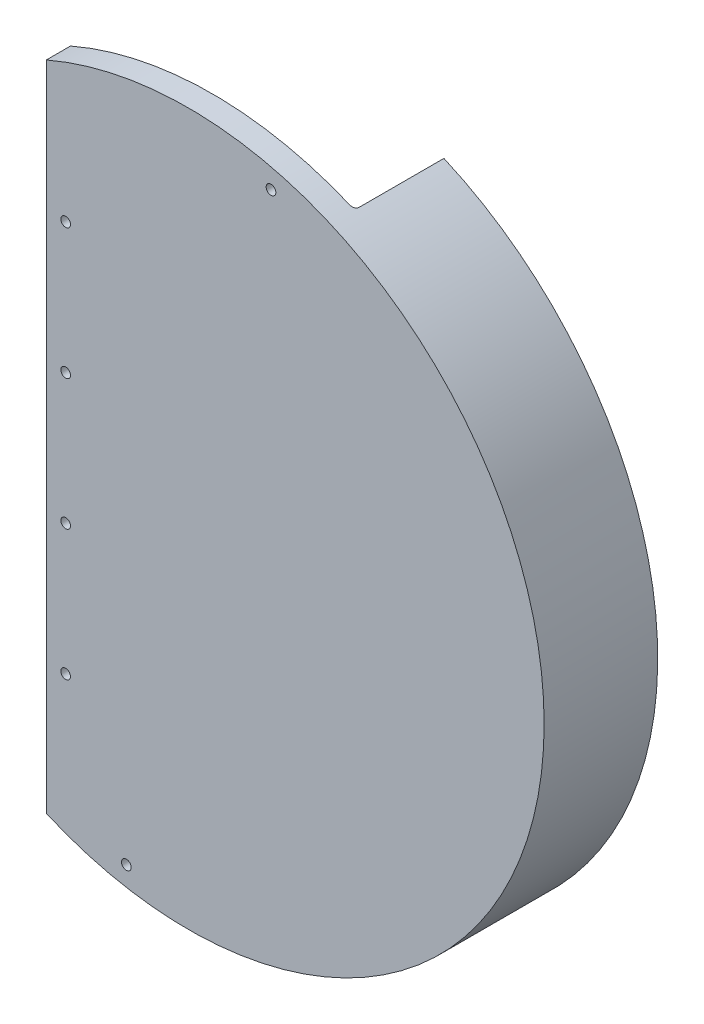
SolidWorks part; units mm, degrees
ref_plane "Front Plane" through (0, 0, 0) normal (0, 0, 1) x (1, 0, 0)
ref_plane "Top Plane" through (0, 0, 0) normal (0, 1, 0) x (1, 0, 0)
ref_plane "Right Plane" through (0, 0, 0) normal (1, 0, 0) x (0, 0, -1)
sketch "Sketch1" plane through (0, 0, 0) normal (0, 0, 1) x (1, 0, 0)
  line L0 (0, -67.5) -> (0, 67.5)
  line L1 (8, -62.0361) -> (8, 62.0361) construction
  line L2 (29.3823, 0) -> (0, -67.5) construction
  line L3 (29.3823, 0) -> (24.8583, -73.4786) construction
  line L4 (20, 73.0174) -> (20, 64.9435) construction
  line L5 (35, 73.4031) -> (35, 65.3768) construction
  line L6 (58.7646, 67.5) -> (55.5716, 60.1648) construction
  line L7 (0, 0) -> (8, 0) construction
  line L8 (4, 69.1036) -> (4, -69.1036) construction
  line L9 (0, 67.5) -> (-23.4948, 67.5) construction
  line L10 (-23.4948, 67.5) -> (-23.4948, 40.5) construction
  line L11 (-23.4948, 40.5) -> (-23.4948, 13.5) construction
  line L12 (-23.4948, 13.5) -> (-23.4948, 40.5) construction
  line L13 (-23.4948, 13.5) -> (-23.4948, -13.5) construction
  line L14 (-23.4948, 40.5) -> (-23.4948, 13.5) construction
  line L15 (-23.4948, -13.5) -> (-23.4948, -40.5) construction
  line L16 (-23.4948, -40.5) -> (-23.4948, -67.5) construction
  line L17 (0, -67.5) -> (-23.4948, -67.5) construction
  line L18 (45.4979, 63.608) -> (47.4627, 71.3629) construction
  line L19 (16.5579, -64.3523) -> (16.5579, -72.4921) construction
  arc A0 (0, 67.5) -> (0, -67.5) centre (29.3823, 0) cw
  arc A1 (8, 62.0361) -> (8, -62.0361) centre (29.3823, 0) cw construction
  circle A2 centre (4, 40.5) radius 1
  circle A3 centre (4, 13.5) radius 1
  circle A4 centre (4, -13.5) radius 1
  circle A5 centre (4, -40.5) radius 1
  circle A6 centre (46.4803, 67.4854) radius 1
  circle A7 centre (16.5579, -68.4222) radius 1
  arc A8 (35, 65.3768) -> (55.5716, 60.1648) centre (29.3823, 0) cw construction
  arc A9 (8, -62.0361) -> (25.3499, -65.4937) centre (29.3823, 0) ccw construction
  point P3 (16.5579, -64.3523)
  point P4 (0, 0)
  point P6 (103, 0)
  point P36 (4, 0)
  point P45 (46.4803, 67.4854)
  dimension "D8" = 2
  dimension "D1" = 135
  dimension "D2" = 103
  dimension "D4" = 20
  dimension "D5" = 160
  dimension "D6" = 20
  dimension "D7" = 15
  dimension "D3" = 8
extrude "Boss-Extrude1" add sketch "Sketch1" along normal blind 5
sketch "Sketch2" plane through (0, 0, 0) normal (0, 0, -1) x (-1, 0, 0)
  line L0 (-58.7646, 67.5) -> (-55.5716, 60.1648)
  line L1 (-25.3499, -65.4937) -> (-24.8583, -73.4786)
  line L2 (-29.3823, 0) -> (0, -67.5) construction
  line L3 (-29.3823, 0) -> (-24.8583, -73.4786) construction
  line L5 (-29.3823, 0) -> (-58.7646, 67.5) construction
  arc A0 (0, 67.5) -> (0, -67.5) centre (-29.3823, 0) ccw construction
  arc A3 (-55.5716, 60.1648) -> (-25.3499, -65.4937) centre (-29.3823, 0) ccw
  arc A4 (-58.7646, 67.5) -> (-24.8583, -73.4786) centre (-29.3823, 0) ccw
  dimension "D5" = 160
  dimension "D2" = 20
  dimension "D1" = 8
extrude "Boss-Extrude2" add sketch "Sketch2" along normal blind 18.5
fillet "Fillet1" radius 1 3 edges at (25.1041, -69.4861, 0) (57.1681, 63.8324, 0) (93.1808, -15.3439, 0)
equation "\"width\"=0.103"
equation "\"height\"=0.135"
equation "\"stop_width\"=0.008"
equation "\"inf_stop_angle\"=20"
equation "\"superior_gap\"=0.015"
equation "\"superior_gap_offset\"=0.02"
equation "\"t\"=0.005"
equation "\"cover_holes_diam\"=0.002"
equation "\"cover_holes_depth\"=0.004"
equation "\"cover_hole_pitch\"=0.0004"
equation "\"D1@Sketch1\"=\"height\"*1000"
equation "\"D2@Sketch1\"=\"width\"*1000"
equation "\"D3@Sketch1\"=\"stop_width\"*1000"
equation "\"D4@Sketch1\"=\"inf_stop_angle\""
equation "\"D6@Sketch1\"=\"superior_gap_offset\"*1000"
equation "\"D7@Sketch1\"=\"superior_gap\"*1000"
equation "\"D8@Sketch1\"=\"cover_holes_diam\"*1000"
equation "\"D1@Boss-Extrude1\"=\"t\"*1000"
equation "\"t2\"=0.0185"
equation "\"D1@Sketch2\"=\"stop_width\"*1000"
equation "\"D2@Sketch2\"=\"inf_stop_angle\""
equation "\"D5@Sketch2\"=160"
equation "\"D1@Boss-Extrude2\"=\"t2\"*1000"
